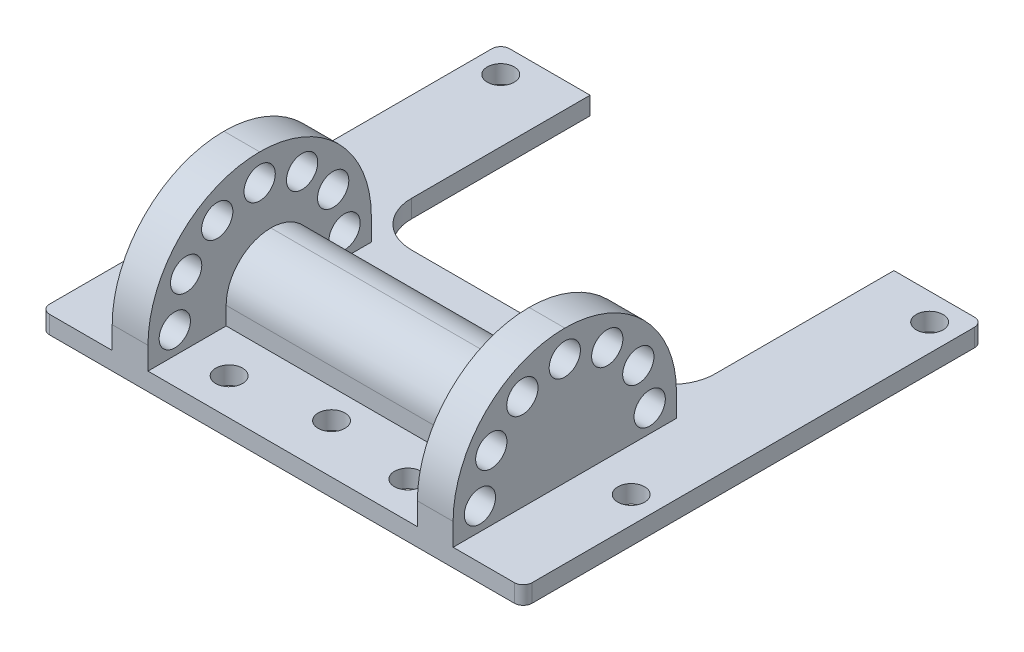
SolidWorks part; units mm, degrees
ref_plane "Front Plane" through (0, 0, 0) normal (0, 0, 1) x (1, 0, 0)
ref_plane "Top Plane" through (0, 0, 0) normal (0, 1, 0) x (1, 0, 0)
ref_plane "Right Plane" through (0, 0, 0) normal (1, 0, 0) x (0, 0, -1)
sketch "Sketch1" plane through (0, 0, 0) normal (0, 1, 0) x (1, 0, 0)
  line L11 (-27.0757, 25.1795) -> (26.9243, 25.1795) construction
  line L16 (26.9243, -19.2205) -> (13.9243, -19.2205) construction
  line L17 (13.9243, -25.2205) -> (-14.0757, -25.2205) construction
  line L18 (-14.0757, -19.2205) -> (-27.0757, -19.2205) construction
  line L19 (-27.0757, 25.1795) -> (-27.0757, -19.2205) construction
  line L20 (-14.0757, -19.2205) -> (-14.0757, -25.2205) construction
  line L21 (13.9243, -19.2205) -> (13.9243, -25.3339) construction
  line L22 (26.9243, 25.1795) -> (26.9243, -19.2205) construction
  line L23 (-17.0757, 5.1795) -> (-17.0757, 25.1795)
  line L24 (-17.0757, 25.1795) -> (-26.0757, 25.1795)
  line L25 (-27.0757, 24.1795) -> (-27.0757, -25.3038)
  line L26 (-26.0757, -26.3038) -> (25.9243, -26.3038)
  line L27 (26.9243, -25.3038) -> (26.9243, 24.1795)
  line L28 (25.9243, 25.1795) -> (16.9243, 25.1795)
  line L29 (16.9243, 25.1795) -> (16.9243, 5.1795)
  line L30 (11.9243, 0.1795) -> (-12.0757, 0.1795)
  circle A5 centre (-24.0757, 22.1795) radius 1.5
  circle A6 centre (23.9243, 22.1795) radius 1.5
  circle A7 centre (-24.0757, -11.2205) radius 1.5
  circle A8 centre (-10.0757, -22.2205) radius 1.5
  circle A9 centre (9.9243, -22.2205) radius 1.5
  arc A10 (16.9243, 5.1795) -> (11.9243, 0.1795) centre (11.9243, 5.1795) cw
  arc A11 (-12.0757, 0.1795) -> (-17.0757, 5.1795) centre (-12.0757, 5.1795) cw
  circle A12 centre (0, -20.8351) radius 1.5
  arc A13 (-26.0757, 25.1795) -> (-27.0757, 24.1795) centre (-26.0757, 24.1795) ccw
  arc A14 (25.9243, 25.1795) -> (26.9243, 24.1795) centre (25.9243, 24.1795) cw
  arc A15 (25.9243, -26.3038) -> (26.9243, -25.3038) centre (25.9243, -25.3038) ccw
  arc A16 (-27.0757, -25.3038) -> (-26.0757, -26.3038) centre (-26.0757, -25.3038) ccw
  circle A17 centre (23.9243, -11.2205) radius 1.5
  point P10 (0, 0)
  point P20 (26.9243, 25.8226)
  point P22 (-16.6312, -1.4023)
  point P29 (-26.2674, 25.1795)
  point P31 (16.9243, 0.1795)
  point P36 (0, -20.8351)
  point P49 (21.2091, -11.2205)
  dimension "D2" = 3
  dimension "D3" = 3
  dimension "D4" = 54
  dimension "D5" = 3
  dimension "D11" = 3
  dimension "D7" = 3
  dimension "D12" = 5
  dimension "D13" = 1
  dimension "D14" = 3
  dimension "D15" = 8
  dimension "D6" = 44.4
  dimension "D8" = 10
  dimension "D9" = 10
  dimension "D10" = 25
extrude "Boss-Extrude1" add sketch "Sketch1" along normal blind 2
sketch "Sketch2" plane through (0, 2, 0) normal (0, 1, 0) x (1, 0, 0)
  line L0 (-26.0757, -26.3038) -> (25.9243, -26.3038) construction
  line L1 (-19.0757, -26.3038) -> (-15.0757, -26.3038)
  line L2 (-19.0757, -26.3038) -> (-19.0757, -1.3038)
  line L3 (-19.0757, -1.3038) -> (-15.0757, -1.3038)
  line L4 (-15.0757, -26.3038) -> (-15.0757, -1.3038)
  line L5 (-27.0757, 24.1795) -> (-27.0757, -25.3038) construction
  dimension "D1" = 8
  dimension "D2" = 4
  dimension "D3" = 25
extrude "Boss-Extrude2" add sketch "Sketch2" along normal blind 15
fillet "Fillet1" radius 12.5 2 edges at (-17.0757, 17, 26.3038) (-17.0757, 17, 1.3038)
sketch "Sketch3" plane through (-15.0757, 0, 0) normal (1, 0, 0) x (0, 0, -1)
  line L0 (-13.8038, 17) -> (-13.8038, 14) construction
  circle A0 centre (-13.8038, 14) radius 1.75
  dimension "D2" = 3.5
  dimension "D1" = 3
extrude "Cut-Extrude3" cut sketch "Sketch3" against normal through all
pattern_circular "CirPattern1" count 4 every 30 about axis through (0, 4.5, 13.8038) along (1, 0, 0) of "Cut-Extrude3"
mirror "Mirror1" about plane through (0, 0, 0) normal (1, 0, 0) of "CirPattern1", "Cut-Extrude3", "Fillet1", "Boss-Extrude2"
sketch "Sketch4" plane through (0, 2, 0) normal (0, 1, 0) x (1, 0, 0)
  line L0 (-15.0757, -13.8038) -> (-15.0757, -1.3038) construction
  line L1 (-15.0757, -7.5538) -> (15.0757, -7.5538)
  line L2 (-15.0757, -7.5538) -> (-15.0757, -17.5538)
  line L3 (-15.0757, -17.5538) -> (15.0757, -17.5538)
  line L4 (15.0757, -7.5538) -> (15.0757, -17.5538)
  line L5 (15.0757, -13.8038) -> (15.0757, -26.3038) construction
  dimension "D1" = 10
extrude "Boss-Extrude3" add sketch "Sketch4" along normal blind 7
fillet "Fillet2" radius 5 2 edges at (0, 9, 17.5538) (0, 9, 7.5538)
